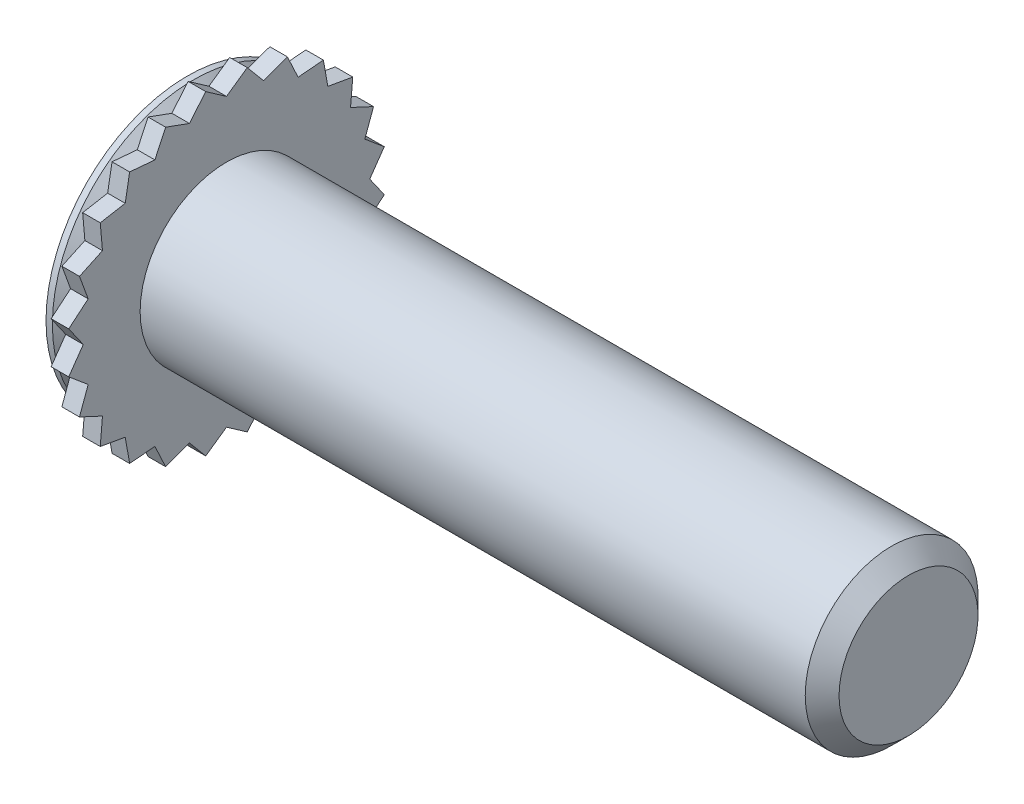
SolidWorks part; units mm, degrees
revolve "BaseBody" add sketch "BodySke" angle 360 about L6 other way angle 15
sketch "BodySke" plane through (0, 0, 0) normal (0, 0, 1) x (1, 0, 0)
  line L0 (0, 2.2225) -> (0, 3.9497)
  line L1 (1.0922, 4.445) -> (0.6007, 4.445)
  line L2 (0.6007, 4.445) -> (0.6007, 3.636)
  line L3 (1.0922, 2.413) -> (19.6698, 2.413)
  line L4 (20.1422, 1.9406) -> (20.1422, 0)
  line L5 (20.1422, 0) -> (0.5461, 0)
  line L6 (0, 0) -> (50.554, 0) construction
  line L7 (1.0922, 4.445) -> (1.0922, 2.413)
  line L8 (20.1422, 1.9406) -> (19.6698, 2.413)
  line L9 (0.6007, 3.636) -> (0.4915, 3.636)
  line L10 (0.4915, 3.636) -> (0.1778, 3.9497)
  line L11 (1.8847, 19.05) -> (1.8847, -3.175) construction
  line L12 (0.1778, 3.9497) -> (0, 3.9497)
  line L13 (0, 2.2225) -> (0.5461, 1.6764)
  line L14 (0.5461, 1.6764) -> (0.5461, 0)
  dimension "Advance" = 0.7925
  dimension "Minor_dia" = 3.8811
  dimension "Diameter" = 4.826
  dimension "Length" = 19.05
  dimension "D1" = 45
cosmetic thread "ThreadCosmetic" [suppressed] parameters "Thread_length"=17.4752, "Thread_minor"=3.8811
ref_plane "Plane1" through (0, 0, 0) normal (0, 0, 1) x (1, 0, 0)
ref_plane "Plane2" through (0, 0, 0) normal (0, 1, 0) x (1, 0, 0)
ref_plane "Plane3" through (0, 0, 0) normal (1, 0, 0) x (0, 0, -1)
sketch "ThdSchSke" plane through (0, 0, 0) normal (0, 0, 1) x (1, 0, 0)
  line L0 (2.667, -1.9406) -> (2.3362, -2.413)
  line L1 (2.667, -1.9406) -> (2.9978, -2.413)
  line L2 (2.9978, -2.413) -> (2.9978, -3.0162)
  line L3 (-3.175, 0) -> (5.1513, 0) construction
  line L5 (2.9978, -3.0162) -> (2.3362, -3.0162)
  line L6 (2.3362, -3.0162) -> (2.3362, -2.413)
  line L8 (1.0922, -2.413) -> (1.0922, 2.413) construction
  dimension "Diameter" = 4.826
  dimension "Thread_minor" = 3.8811
  dimension "Start" = 1.5748
revolve "ThreadSchematic" [suppressed] cut sketch "ThdSchSke" angle 360 about L3
pattern_linear "ThdSchPat" [suppressed]
sketch "CliRinCutSke" plane through (1.0922, 0, 0) normal (1, 0, 0) x (0, 0, -1)
  line L0 (0, 0) -> (0, 4.8256) construction
  line L1 (0.5802, 4.407) -> (0, 4.0005)
  line L2 (0, 4.0005) -> (-0.5802, 4.407)
  arc A0 (0.5802, 4.407) -> (-0.5802, 4.407) centre (0, 0) ccw
  circle A1 centre (0, 0) radius 4.445 construction
  circle A2 centre (0, 0) radius 4.0005 construction
extrude "ClinchCut" cut sketch "CliRinCutSke" against normal blind 0.4915
pattern_circular "ClinchCutPat" count 24 every 15 about axis through (0, 0, 0) along (1, 0, 0) of "ClinchCut"
equation "' \"Length@BodySke\" = 0.75"
equation "' \"A_dim@BodySke\" = 0.043"
equation "' \"E_dia@BodySke\" = 0.35"
equation "' \"C_dia@BodySke\" = 0.311"
equation "' \"Diameter@BodySke\" = 0.19"
equation "' \"Minor_dia@BodySke\" = 0.1528"
equation "' \"Advance@BodySke\" = 0.0312"
equation "\"Face_clr_dia@BodySke\" = \"E_dia@BodySke\" / 2"
equation "\"Face_clr_dep@BodySke\" = \"A_dim@BodySke\" / 2"
equation "\"Start@ThdSchSke\" = 0.062"
equation "\"Skirt_ht@BodySke\" = \"A_dim@BodySke\" * 0.45"
equation "\"Clinch_ht@BodySke\" = \"A_dim@BodySke\" * 0.45"
equation "\"Depth@ClinchCut\" = \"A_dim@BodySke\" * 0.45"
equation "\"Count@ClinchCutPat\" = 24"
equation "\"Angle@ClinchCutPat\" = 360 / \"Count@ClinchCutPat\""
equation "\"Angle@CliRinCutSke\" = 360 / \"Count@ClinchCutPat\""
equation "\"Clinch_minor@CliRinCutSke\" =  \"C_dia@BodySke\" "
equation "\"Clinch_minor@CliRinCutSke\" =  \"E_dia@BodySke\" * 0.9"
equation "\"Thread_length@ThreadCosmetic\" = \"Length@BodySke\" - \"Start@ThdSchSke\""
equation "\"Thread_minor@ThreadCosmetic\" = \"Minor_dia@BodySke\""
equation "\"Thread_minor@ThdSchSke\" = \"Minor_dia@BodySke\""
equation "\"Diameter@ThdSchSke\" = \"Diameter@BodySke\""
equation "\"Overcut@ThdSchSke\" = \"Diameter@BodySke\" * 1.25"
equation "\"Num_threads@ThdSchPat\" = int( \"Thread_length@ThreadCosmetic\" / \"Advance@BodySke\" + 0.999 )  + 1"
equation "\"Advance@ThdSchPat\" = \"Thread_length@ThreadCosmetic\" /  (\"Num_threads@ThdSchPat\" - 1) 'relax it"
equation "\"Num_threads@ThdSchPat\" = \"Num_threads@ThdSchPat\" - sgn( \"Num_threads@ThdSchPat\" - 1) '---chamfered tips only---"
